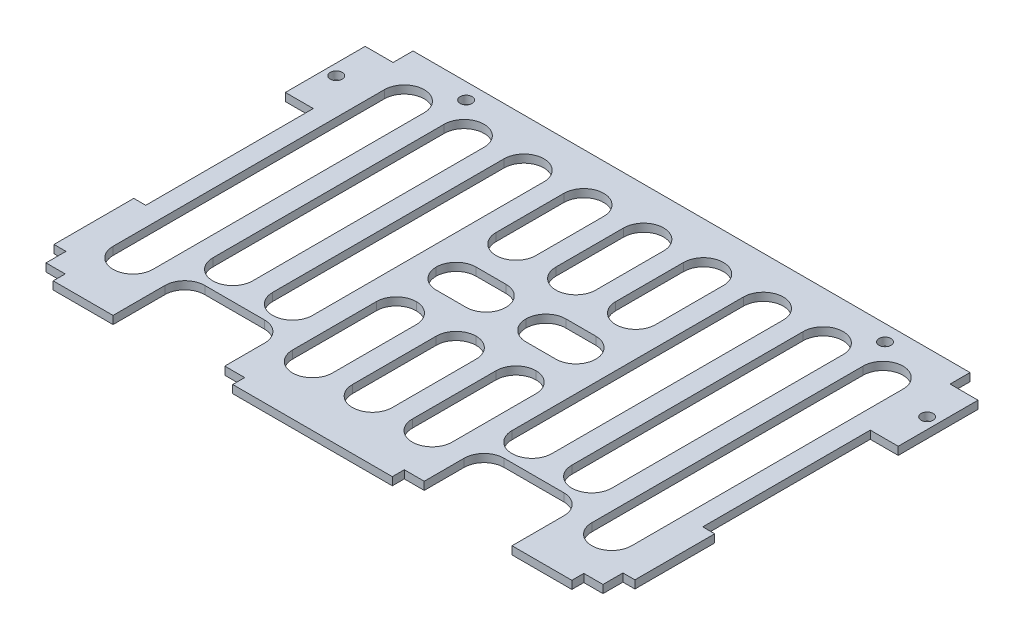
SolidWorks part; units mm, degrees
material "A-玻璃纤维"
ref_plane "前视基准面" through (0, 0, 0) normal (0, 0, 1) x (1, 0, 0)
ref_plane "上视基准面" through (0, 0, 0) normal (0, 1, 0) x (1, 0, 0)
ref_plane "右视基准面" through (0, 0, 0) normal (1, 0, 0) x (0, 0, -1)
sketch "草图1" plane through (0, 0, 0) normal (0, 1, 0) x (1, 0, 0)
  line L1 (-69.805, 46) -> (69.805, 46)
  line L2 (-69.805, 46) -> (-69.805, -46)
  line L3 (-69.805, -46) -> (69.805, -46)
  line L4 (69.805, 46) -> (69.805, -46)
  line L5 (0, -46) -> (0, 46) construction
  line L6 (-69.805, 0) -> (69.805, 0) construction
  point P0 (0, 0)
  dimension "D1" = 139.61
  dimension "D2" = 92
extrude "凸台-拉伸1" add sketch "草图1" along normal blind 2
sketch "草图2" plane through (0, 0, 46) normal (0, 0, 1) x (1, 0, 0)
  line L0 (-69.805, 2) -> (69.805, 2) construction
  line L1 (-20, 2) -> (20, 2)
  line L2 (-20, 2) -> (-20, 0)
  line L3 (-20, 0) -> (20, 0)
  line L4 (20, 2) -> (20, 0)
  line L5 (-69.805, 0) -> (69.805, 0) construction
  line L6 (0, 7.6017) -> (0, -13.3815) construction
  line L7 (65, 2) -> (65, 0)
  line L8 (-65, 2) -> (-50, 2)
  line L9 (-65, 2) -> (-65, 0)
  line L10 (-65, 0) -> (-50, 0)
  line L11 (-50, 2) -> (-50, 0)
  line L12 (65, 2) -> (50, 2)
  line L13 (65, 0) -> (50, 0)
  line L14 (50, 2) -> (50, 0)
  dimension "D1" = 40
  dimension "D2" = 15
  dimension "D3" = 30
extrude "凸台-拉伸2" add sketch "草图2" along normal blind 3
sketch "草图3" plane through (69.805, 0, 0) normal (1, 0, 0) x (0, 0, -1)
  line L1 (46, 2) -> (46, 0) construction
  line L2 (-46, 2) -> (46, 2) construction
  line L3 (-46, 0) -> (46, 0) construction
  line L7 (0, 0) -> (0, 7.9206) construction
  line L8 (41, 2) -> (41, 0)
  line L9 (41, 0) -> (21, 0)
  line L10 (41, 2) -> (21, 2)
  line L11 (21, 2) -> (21, 0)
  dimension "D1" = 20
  dimension "D2" = 5
extrude "凸台-拉伸3" add sketch "草图3" along normal blind 7
sketch "草图4" plane through (0, 2, 0) normal (0, 1, 0) x (1, 0, 0)
  line L0 (69.805, 46) -> (-69.805, 46) construction
  line L1 (69.805, -46) -> (69.805, 21) construction
  circle A0 centre (74.055, 31) radius 1.5
  dimension "D1" = 15
  dimension "D2" = 4.25
  dimension "D3" = 3
extrude "切除-拉伸1" cut sketch "草图4" against normal through all
sketch "草图5" plane through (0, 2, 0) normal (0, 1, 0) x (1, 0, 0)
  line L0 (-60, -34) -> (-60, 34) construction
  line L1 (-65, -34) -> (-65, 34)
  line L2 (-55, -34) -> (-55, 34)
  line L3 (69.805, 46) -> (-69.805, 46) construction
  line L4 (-69.805, 46) -> (-69.805, -46) construction
  arc A0 (-65, -34) -> (-55, -34) centre (-60, -34) ccw
  arc A1 (-55, 34) -> (-65, 34) centre (-60, 34) ccw
  point P2 (-60, 0)
  dimension "D1" = 10
  dimension "D2" = 68
  dimension "D3" = 46
  dimension "D4" = 4.805
extrude "切除-拉伸2" cut sketch "草图5" against normal through all
pattern_linear "阵列(线性)1" count 9 spacing 15 along (1, 0, 0) of "切除-拉伸2"
sketch "草图8" plane through (0, 0, 0) normal (0, -1, 0) x (1, 0, 0)
  line L0 (55, -34) -> (55, 34) construction
  line L1 (69.805, -46) -> (-69.805, -46) construction
  circle A0 centre (52.5, -42) radius 1.5
  dimension "D1" = 2.5
  dimension "D3" = 3
  dimension "D2" = 4
extrude "切除-拉伸4" cut sketch "草图8" against normal through all
mirror "镜向4" about plane through (0, 0, 0) normal (1, 0, 0) of "切除-拉伸4"
sketch "草图9" plane through (0, 0, 0) normal (0, -1, 0) x (1, 0, 0)
  line L0 (-5, -34) -> (-5, 34) construction
  line L1 (-5, -12) -> (5, -12)
  line L2 (-5, -12) -> (-5, -4)
  line L3 (-5, -4) -> (5, -4)
  line L4 (5, -12) -> (5, -4)
  line L5 (5, 34) -> (5, -34) construction
  line L6 (69.805, -46) -> (-69.805, -46) construction
  circle A0 centre (0, -8) radius 1.5
  dimension "D1" = 3
  dimension "D2" = 38
  dimension "D3" = 4
  dimension "D4" = 8
sketch "草图10" plane through (0, 2, 0) normal (0, 1, 0) x (1, 0, 0)
  line L0 (25, -29) -> (50, -29)
  line L1 (25, 34) -> (25, -34) construction
  line L2 (50, -34) -> (50, 34) construction
  line L3 (50, -29) -> (50, -34)
  line L4 (50, -34) -> (25, -34)
  line L5 (25, -34) -> (25, -29)
  line L6 (-50, -34) -> (-25, -34)
  line L7 (-50, 34) -> (-50, -34) construction
  line L8 (-25, -34) -> (-25, 34) construction
  line L9 (-25, -34) -> (-25, -29)
  line L10 (-25, -29) -> (-50, -29)
  line L11 (-50, -29) -> (-50, -34)
  line L12 (-50, -46) -> (-20, -46) construction
  dimension "D1" = 12
  dimension "D2" = 5
extrude "凸台-拉伸5" add sketch "草图10" against normal up to surface (2 mm away) up to face at (-52.5, 0, -43.5)
sketch "草图12" plane through (0, 2, 0) normal (0, 1, 0) x (1, 0, 0)
  line L0 (-50, -46) -> (-50, -31)
  line L1 (-50, -31) -> (-25, -31)
  line L2 (-25, -31) -> (-25, -46)
  line L3 (-50, -46) -> (-20, -46) construction
  line L4 (-25, -46) -> (-50, -46)
  line L5 (25, -31) -> (25, -46)
  line L6 (20, -46) -> (50, -46) construction
  line L7 (25, -31) -> (50, -31)
  line L8 (50, -31) -> (50, -46)
  line L9 (50, -46) -> (25, -46)
  line L11 (0, -49) -> (0, -23.8742) construction
  line L12 (20, -49) -> (-20, -49) construction
  line L13 (-50, 34) -> (-50, -29) construction
  line L14 (25, 34) -> (25, -29) construction
  line L15 (-25, -29) -> (-25, 34) construction
  dimension "D1" = 15
extrude "切除-拉伸5" cut sketch "草图12" against normal through all
fillet "圆角1" radius 5 12 edges at (-40, 1, 29) (-50, 1, 29) (-25, 1, 31) (-50, 1, 31) (50, 1, 31) (25, 1, 31) (50, 1, 29) (40, 1, 29) (35, 1, 29) (25, 1, 29) (-25, 1, 29) (-35, 1, 29)
sketch "草图13" plane through (0, 2, 0) normal (0, 1, 0) x (1, 0, 0)
  line L0 (-10, 2) -> (10, 2) construction
  line L1 (-10, -34) -> (-10, 34) construction
  line L2 (10, 34) -> (10, -34) construction
  line L3 (-10, 7) -> (10, 7)
  line L4 (-10, -3) -> (10, -3)
  arc A0 (-10, 7) -> (-10, -3) centre (-10, 2) ccw
  arc A1 (10, -3) -> (10, 7) centre (10, 2) ccw
  point P8 (0, 2)
  dimension "D1" = 6
  dimension "D2" = 10
extrude "切除-拉伸6" cut sketch "草图13" against normal through all
sketch "草图14" plane through (0, 2, 0) normal (0, 1, 0) x (1, 0, 0)
  line L0 (20, 7) -> (2.5, 7)
  line L1 (-20, 34) -> (-20, -34) construction
  line L2 (20, -34) -> (20, 34) construction
  line L3 (-20, -3) -> (-2.5, -3)
  line L4 (5, -3) -> (10, -3) construction
  line L5 (10, 7) -> (5, 7) construction
  line L6 (-20, -8) -> (20, -8)
  line L7 (-20, 12) -> (20, 12)
  line L8 (20, 12) -> (20, 7)
  line L9 (20, -3) -> (20, -8)
  line L10 (-20, -3) -> (-20, -8)
  line L11 (-20, 7) -> (-20, 12)
  line L12 (-2.5, 7) -> (-2.5, -3)
  line L13 (2.5, 7) -> (2.5, -3)
  line L14 (2.5, -3) -> (20, -3)
  line L15 (-2.5, 7) -> (-20, 7)
  dimension "D1" = 5
  dimension "D2" = 5
  dimension "D3" = 5
  dimension "D4" = 2.5
extrude "凸台-拉伸6" add sketch "草图14" against normal up to surface (2 mm away) up to face at (-45, 0, 1.2142)
fillet "圆角2" radius 5 20 edges at (-10, 1, -12) (-20, 1, -12) (-5, 1, -12) (5, 1, -12) (10, 1, -12) (20, 1, -12) (20, 1, 3) (20, 1, -7) (20, 1, 8) (10, 1, 8) (-5, 1, 8) (5, 1, 8) (-10, 1, 8) (-20, 1, 8) (2.5, 1, 3) (2.5, 1, -7) (-2.5, 1, 3) (-2.5, 1, -7) (-20, 1, 3) (-20, 1, -7)
mirror "镜向5" about plane through (0, 0, 0) normal (1, 0, 0) of "切除-拉伸1", "凸台-拉伸3"
sketch "草图15" plane through (0, 2, 0) normal (0, 1, 0) x (1, 0, 0)
  line L0 (-78.6794, 0) -> (88.0446, 0) construction
  line L2 (69.805, -21) -> (72.805, -21)
  line L3 (69.805, -46) -> (69.805, 21) construction
  line L4 (72.805, -21) -> (72.805, -41)
  line L5 (72.805, -41) -> (69.805, -41)
  line L8 (69.805, -21) -> (69.805, -41)
  line L9 (0, 53.8419) -> (0, -65.7396) construction
  line L10 (-69.805, -21) -> (-69.805, -41)
  line L11 (-72.805, -41) -> (-69.805, -41)
  line L12 (-72.805, -21) -> (-72.805, -41)
  line L13 (-69.805, -21) -> (-72.805, -21)
  dimension "D1" = 21
  dimension "D2" = 20
  dimension "D3" = 3
extrude "凸台-拉伸7" add sketch "草图15" against normal up to surface (2 mm away) up to face at (-74.055, 0, -29.5)
